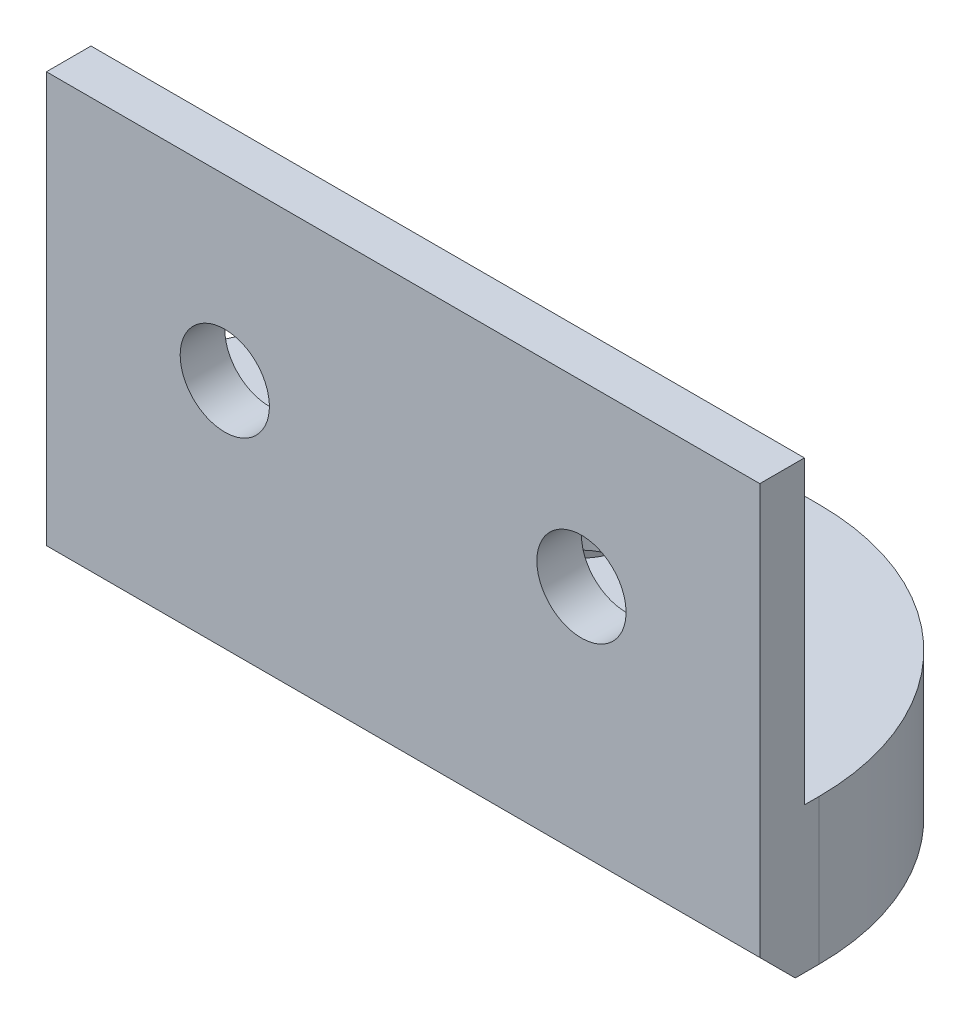
SolidWorks part; units mm, degrees
ref_plane "Front Plane" through (0, 0, 0) normal (0, 0, 1) x (1, 0, 0)
ref_plane "Top Plane" through (0, 0, 0) normal (0, 1, 0) x (1, 0, 0)
ref_plane "Right Plane" through (0, 0, 0) normal (1, 0, 0) x (0, 0, -1)
sketch "Sketch1" plane through (0, 0, 0) normal (0, 0, 1) x (1, 0, 0)
  line L0 (-25.4, 0) -> (25.4, 0) construction
  line L1 (25.4, -12.7) -> (-25.4, -12.7)
  line L2 (25.4, -12.7) -> (25.4, 12.7)
  line L3 (25.4, 12.7) -> (-25.4, 12.7)
  line L4 (-25.4, -12.7) -> (-25.4, 12.7)
  line L5 (25.4, -12.7) -> (-25.4, 12.7) construction
  line L6 (25.4, 12.7) -> (-25.4, -12.7) construction
  point P0 (0, 0)
  point P8 (-12.7, 0)
  point P9 (12.7, 0)
  dimension "D1" = 25.4
  dimension "D2" = 50.8
  dimension "D3" = 12.7
  dimension "D4" = 12.7
extrude "Boss-Extrude1" add sketch "Sketch1" along normal blind 3.175 contours L2 L1 L4 L3
hole_wizard "1/4 (0.25) Diameter Hole1" positions "Sketch2" profile "Sketch3" hole size "1/4" standard "ANSI Inch" end condition through all
sketch "Sketch2" plane through (0, 0, 0) normal (0, 0, -1) x (-1, 0, 0)
  point P0 (-12.7, 0)
  point P3 (12.7, 0)
sketch "Sketch3" plane through (12.7, 0, 0) normal (1, 0, 0) x (0, 1, 0)
  line L0 (0, 0) -> (0, 3.175)
  line L1 (0, 3.175) -> (3.175, 3.175)
  line L2 (3.175, 3.175) -> (3.175, 0)
  line L5 (3.175, 0) -> (0, 0)
  line L11 (0, -6.35) -> (0, 107.95) construction
  dimension "Thru Hole Dia." = 6.35
  dimension "Thru Hole Depth" = 3.175
sketch "Sketch4" plane through (0, 0, 0) normal (0, 0, -1) x (-1, 0, 0)
  line L0 (25.4, -12.7) -> (25.4, 12.7) construction
  line L1 (-25.4, -12.7) -> (25.4, -12.7)
  line L2 (-25.4, -12.7) -> (-25.4, -8.7)
  line L3 (-25.4, -8.7) -> (25.4, -8.7)
  line L4 (25.4, -12.7) -> (25.4, -8.7)
  line L6 (-25.4, -12.7) -> (25.4, -12.7)
  line L7 (-25.4, -12.7) -> (-25.4, -19.05)
  line L8 (-25.4, -19.05) -> (25.4, -19.05)
  line L9 (25.4, -12.7) -> (25.4, -19.05)
  line M7 (-25.4, 12.7) -> (-25.4, -12.7)
  line M8 (-25.4, -12.7) -> (25.4, -12.7)
  line M9 (25.4, -12.7) -> (25.4, 12.7)
  dimension "D1" = 4
  dimension "D2" = 6.35
extrude "Boss-Extrude2" add sketch "Sketch4" along normal blind 19.05 contours L9 L7 L8 M8 | L3 M7 M8 M9 region at (0, -10.7, 0) region at (0, -15.875, 0)
sketch "Sketch5" plane through (0, -19.05, 0) normal (0, -1, 0) x (1, 0, 0)
  line L0 (25.4, -9.525) -> (-25.4, -9.525) construction
  line L1 (25.4, -19.05) -> (25.4, 0) construction
  line L2 (-25.4, -19.05) -> (-25.4, 0) construction
  line L4 (-3.2996, -15.24) -> (3.2996, -15.24)
  line L5 (3.2996, -15.24) -> (6.5991, -9.525)
  line L6 (6.5991, -9.525) -> (3.2996, -3.81)
  line L7 (3.2996, -3.81) -> (-3.2996, -3.81)
  line L8 (-3.2996, -3.81) -> (-6.5991, -9.525)
  line L9 (-6.5991, -9.525) -> (-3.2996, -15.24)
  circle A0 centre (0, -9.525) radius 5.715 construction
  point P7 (-6.5991, -6.35)
  dimension "D1" = 11.43
extrude "Cut-Extrude1" cut sketch "Sketch5" against normal blind 6.35
hole_wizard "1/4 (0.25) Diameter Hole2" positions "Sketch8" profile "Sketch9" hole size "1/4" standard "ANSI Inch" end condition through all
sketch "Sketch8" plane through (0, -19.05, 0) normal (0, -1, 0) x (-1, 0, 0)
  point P0 (0, 9.525)
sketch "Sketch9" plane through (0, -19.05, -9.525) normal (1, 0, 0) x (0, 0, -1)
  line L0 (0, 0) -> (0, 31.75)
  line L1 (0, 31.75) -> (3.175, 31.75)
  line L2 (3.175, 31.75) -> (3.175, 0)
  line L5 (3.175, 0) -> (0, 0)
  line L11 (0, -6.35) -> (0, 107.95) construction
  dimension "Thru Hole Dia." = 6.35
  dimension "Thru Hole Depth" = 31.75
fillet "Fillet1" radius 18 2 edges at (-25.4, -13.875, -19.05) (25.4, -13.875, -19.05)
chamfer "Chamfer1" distance 7 angle 45 1 edges at (0, -12.7, 0)
